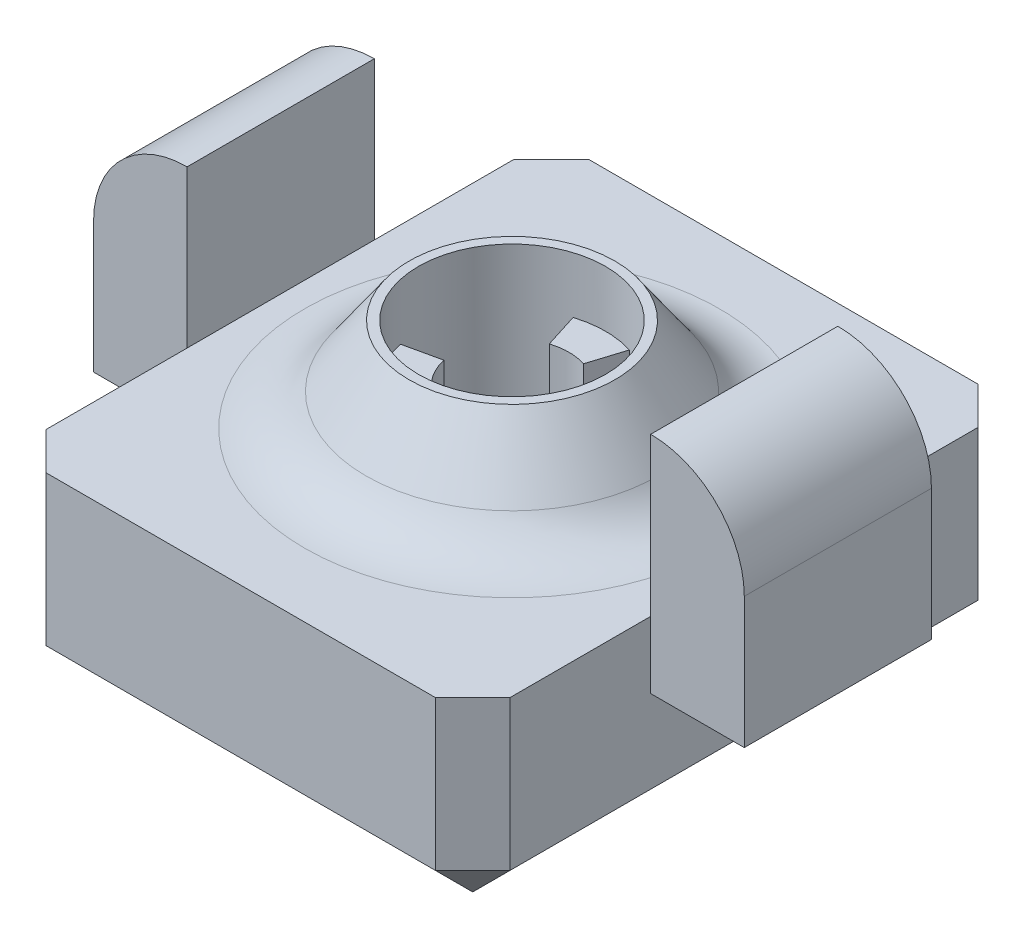
SolidWorks part; units mm, degrees
ref_plane "Front Plane" through (0, 0, 0) normal (0, 0, 1) x (1, 0, 0)
ref_plane "Top Plane" through (0, 0, 0) normal (0, 1, 0) x (1, 0, 0)
ref_plane "Right Plane" through (0, 0, 0) normal (1, 0, 0) x (0, 0, -1)
sketch "Sketch1" plane through (0, 0, 0) normal (0, 1, 0) x (1, 0, 0)
  line L1 (-12.4, 14.5) -> (12.4, 14.5)
  line L2 (-12.4, 14.5) -> (-12.4, -14.5)
  line L3 (-12.4, -14.5) -> (12.4, -14.5)
  line L4 (12.4, 14.5) -> (12.4, -14.5)
  line L5 (-12.4, 14.5) -> (12.4, -14.5) construction
  line L6 (-12.4, -14.5) -> (12.4, 14.5) construction
  point P0 (0, 0)
  dimension "D1" = 29
  dimension "D2" = 24.8
extrude "Boss-Extrude1" add sketch "Sketch1" along normal mid plane 10
sketch "Sketch2" plane through (0, 5, 0) normal (0, 1, 0) x (1, 0, 0)
  circle A0 centre (0, 0) radius 9
  dimension "D1" = 18
extrude "Boss-Extrude2" add sketch "Sketch2" along normal blind 5.8 draft 35
sketch "Sketch4" plane through (0, 10.8, 0) normal (0, 1, 0) x (1, 0, 0)
  circle A0 centre (0, 0) radius 5
  dimension "D1" = 10
extrude "Cut-Extrude2" cut sketch "Sketch4" against normal through all
sketch "Sketch5" plane through (0, -5, 0) normal (0, 1, 0) x (1, 0, 0)
  line L0 (0, 3.05) -> (0, -5.1) construction
  line L1 (-1.5336, 4.864) -> (-0.9172, 2.9088)
  line L4 (1.5336, 4.864) -> (0.9172, 2.9088)
  line L14 (3.4455, -3.7601) -> (2.0606, -2.2487)
  line L15 (4.9791, -1.1038) -> (2.9777, -0.6601)
  line L16 (-4.9791, -1.1038) -> (-2.9777, -0.6601)
  line L17 (-3.4455, -3.7601) -> (-2.0606, -2.2487)
  circle A0 centre (0, 0) radius 5.1 construction
  circle A1 centre (0, 0) radius 3.05 construction
  arc A2 (-0.9172, 2.9088) -> (0.9172, 2.9088) centre (0, 0) cw
  arc A5 (-1.5336, 4.864) -> (1.5336, 4.864) centre (0, 0) cw
  arc A6 (4.9791, -1.1038) -> (3.4455, -3.7601) centre (0, 0) cw
  arc A7 (2.9777, -0.6601) -> (2.0606, -2.2487) centre (0, 0) cw
  arc A8 (-3.4455, -3.7601) -> (-4.9791, -1.1038) centre (0, 0) cw
  arc A9 (-2.0606, -2.2487) -> (-2.9777, -0.6601) centre (0, 0) cw
  dimension "D1" = 6.1
  dimension "D2" = 10.2
  dimension "D3" = 35
  dimension "D4" = 3
extrude "Boss-Extrude3" add sketch "Sketch5" along normal blind 12 from surface starting at face at (0, -5, 5)
chamfer "Chamfer1" distance 2 angle 45 8 edges at (0, -5, -14.5) (-12.4, 0, -14.5) (-12.4, -5, 0) (12.4, 0, -14.5) (12.4, -5, 0) (12.4, 0, 14.5) (0, -5, 14.5) (-12.4, 0, 14.5)
fillet "Fillet2" radius 4 1 edges at (0, 5, 9)
sketch "Sketch6" plane through (0, 0, 14.5) normal (0, 0, 1) x (1, 0, 0)
  line L0 (10.4, -5) -> (-10.4, -5) construction
  line L1 (-15, 12) -> (15, 12)
  line L2 (-15, 12) -> (-15, 10)
  line L3 (-15, 10) -> (15, 10)
  line L4 (15, 12) -> (15, 10)
  line L5 (-10.4, 5) -> (10.4, 5) construction
  point P4 (0, 10)
  point P7 (0, -5)
  dimension "D1" = 2
  dimension "D2" = 30
  dimension "D3" = 5
extrude "Cut-Extrude3" cut sketch "Sketch6" against normal through all
chamfer "Chamfer2" [suppressed] distance 1 angle 45
sketch "Sketch7" plane through (-12.4, 0, 0) normal (-1, 0, 0) x (0, 0, 1)
  line L1 (-5.042, 13.387) -> (4.958, 13.387)
  line L2 (-5.042, 13.387) -> (-5.042, 1.387)
  line L3 (-5.042, 1.387) -> (4.958, 1.387)
  line L4 (4.958, 13.387) -> (4.958, 1.387)
  dimension "D1" = 12
  dimension "D2" = 10
extrude "Boss-Extrude4" add sketch "Sketch7" along normal blind 5
sketch "Sketch9" plane through (12.4, 0, 0) normal (1, 0, 0) x (0, 0, -1)
  line L1 (-4.9884, 13.4252) -> (5.0116, 13.4252)
  line L2 (-4.9884, 13.4252) -> (-4.9884, 1.4252)
  line L3 (-4.9884, 1.4252) -> (5.0116, 1.4252)
  line L4 (5.0116, 13.4252) -> (5.0116, 1.4252)
  dimension "D1" = 12
  dimension "D2" = 10
extrude "Boss-Extrude5" add sketch "Sketch9" along normal blind 5
fillet "Fillet3" radius 5 2 edges at (17.4, 13.4252, -0.0116) (-17.4, 13.387, -0.042)
